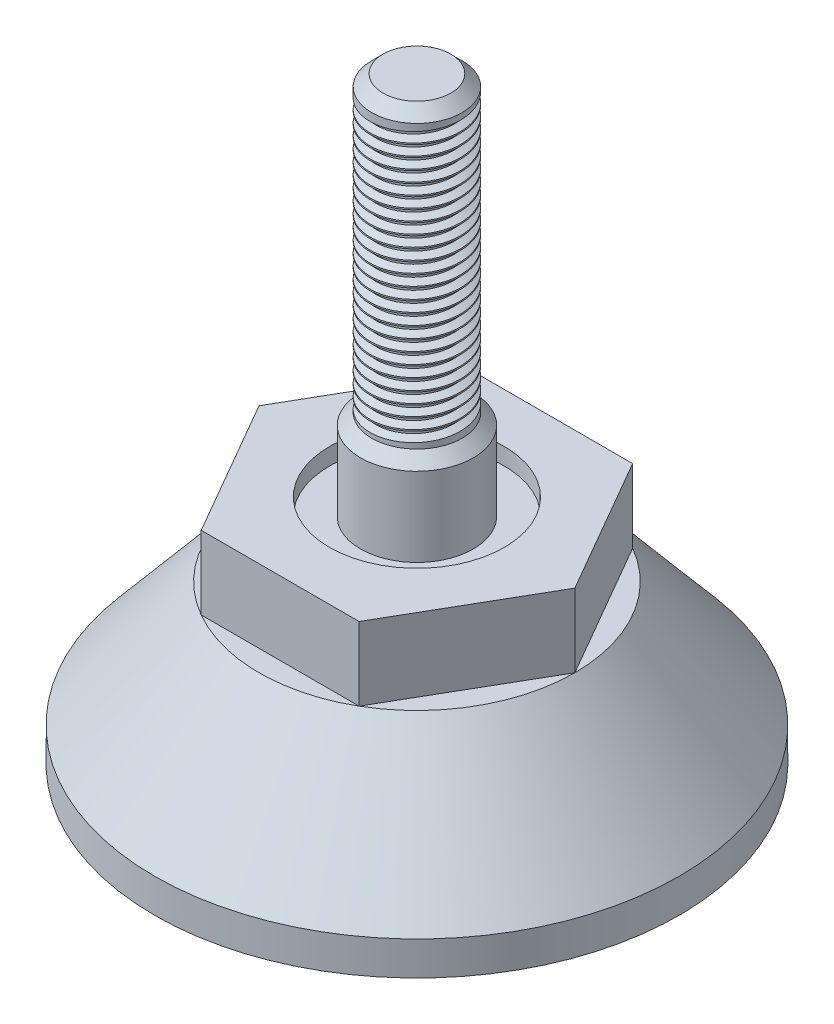
SolidWorks part; units mm, degrees
ref_plane "Спереди" through (0, 0, 0) normal (0, 0, 1) x (1, 0, 0)
ref_plane "Сверху" through (0, 0, 0) normal (0, 1, 0) x (1, 0, 0)
ref_plane "Справа" through (0, 0, 0) normal (1, 0, 0) x (0, 0, -1)
sketch "Эскиз1" plane through (0, 0, 0) normal (0, 0, 1) x (1, 0, 0)
  line L0 (0, 0) -> (23.25, 0)
  line L1 (23.25, 0) -> (23.25, 3)
  line L2 (0, 14) -> (0, 0)
  line L3 (0, 14) -> (14, 14)
  line L4 (14, 14) -> (23.25, 3)
  dimension "D1" = 23.25
  dimension "D2" = 14
  dimension "D3" = 14.3723
  dimension "D4" = 220.061
revolve "Повернуть1" add sketch "Эскиз1" angle 360 about L2
sketch "Эскиз2" plane through (0, 14, 0) normal (0, 1, 0) x (1, 0, 0)
  line L1 (14, 0) -> (7, 12.1244)
  line L2 (7, 12.1244) -> (-7, 12.1244)
  line L3 (-7, 12.1244) -> (-14, 0)
  line L4 (-14, 0) -> (-7, -12.1244)
  line L5 (-7, -12.1244) -> (7, -12.1244)
  line L6 (7, -12.1244) -> (14, 0)
  circle A0 centre (0, 0) radius 14 construction
  circle A1 centre (0, 0) radius 12.1244 construction
extrude "Бобышка-Вытянуть1" add sketch "Эскиз2" along normal blind 6.5
sketch "Эскиз3" plane through (0, 20.5, 0) normal (0, 1, 0) x (1, 0, 0)
  circle A0 centre (0, 0) radius 7.75
  dimension "D1" = 15.5
extrude "Вырез-Вытянуть1" cut sketch "Эскиз3" against normal blind 1.5
sketch "Эскиз4" plane through (0, 19, 0) normal (0, 1, 0) x (1, 0, 0)
  circle A0 centre (0, 0) radius 5
  dimension "D1" = 10
extrude "Бобышка-Вытянуть2" add sketch "Эскиз4" along normal blind 8
chamfer "Фаска1" distance 1 angle 45 1 edges at (0, 27, 5)
sketch "Эскиз5" plane through (0, 27, 0) normal (0, 1, 0) x (1, 0, 0)
  circle A0 centre (0, 0) radius 4
extrude "Бобышка-Вытянуть3" add sketch "Эскиз5" along normal blind 26
chamfer "Фаска2" distance 1 angle 45 1 edges at (0, 53, 4)
thread "Резьба1" pitch 1 method cut profile "Профиль резьбы1" start angle 0, offset 0, length 24, pitch 1, diameter 8
ref_plane "Плоскость1" through (-4, 52, 0) normal (0, 0, 1) x (-1, 0, 0)
sketch "Профиль резьбы1" plane through (-4, 52, 0) normal (0, 0, 1) x (-1, 0, 0)
  line L0 (0, 0) -> (0, 1) construction
  line L11 (0, 0) -> (0, 0.875)
  line L12 (0, 0.875) -> (-0.5413, 0.5625)
  line L13 (-0.5413, 0.5625) -> (-0.5413, 0.3125)
  line L15 (-0.5413, 0.3125) -> (0, 0)
  line L17 (-0.5413, 0.4375) -> (0, 0.4375) construction
  point P2 (0, 0)
  dimension "Pitch" = 1
  dimension "Profile_Angle" = 60
  dimension "Profile_Land" = 0.25
  dimension "Profile_Height" = 0.5413
